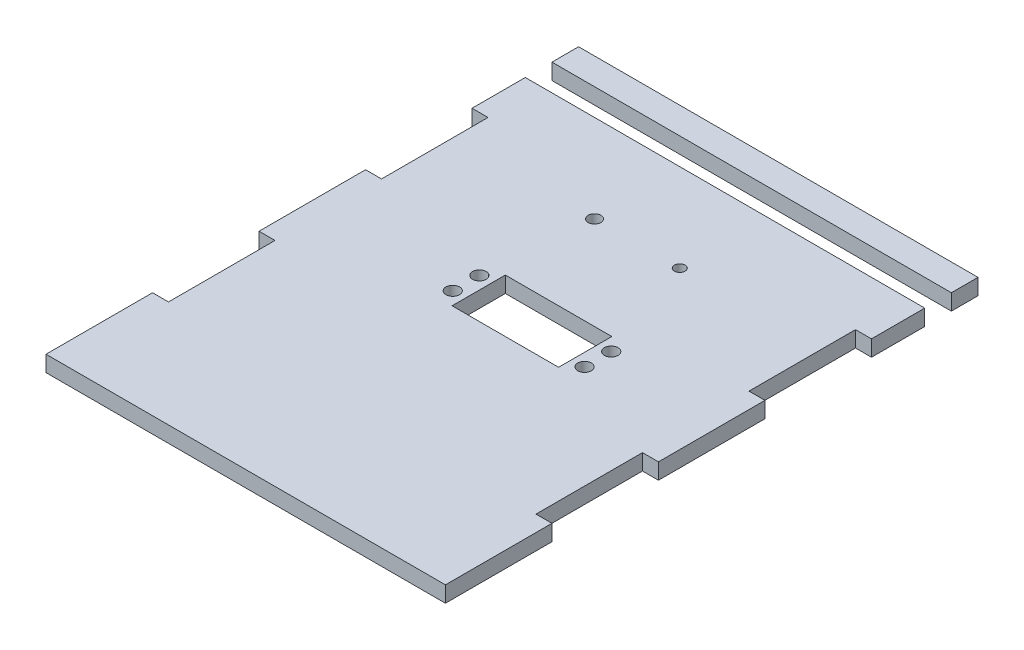
SolidWorks part; units mm, degrees
material "Pine"
ref_plane "Front Plane" through (0, 0, 0) normal (0, 0, 1) x (1, 0, 0)
ref_plane "Top Plane" through (0, 0, 0) normal (0, 1, 0) x (1, 0, 0)
ref_plane "Right Plane" through (0, 0, 0) normal (1, 0, 0) x (0, 0, -1)
sketch "Sketch1" plane through (0, 0, 0) normal (0, 1, 0) x (1, 0, 0)
  line L1 (-75, 100) -> (75, 100)
  line L2 (-75, 100) -> (-75, -100)
  line L3 (-75, -100) -> (75, -100)
  line L4 (75, 100) -> (75, -100)
  line L5 (-75, 100) -> (75, -100) construction
  line L6 (-75, -100) -> (75, 100) construction
  point P0 (0, 0)
  dimension "D1" = 150
  dimension "D2" = 200
extrude "Boss-Extrude1" add sketch "Sketch1" along normal blind 6
sketch "Sketch2" plane through (0, 6, 0) normal (0, 1, 0) x (1, 0, 0)
  line L0 (-75, 100) -> (-75, -100) construction
  line L1 (-75, 60) -> (-69, 60)
  line L2 (-75, 60) -> (-75, 20)
  line L3 (-75, 20) -> (-69, 20)
  line L4 (-69, 60) -> (-69, 20)
  line L5 (75, 100) -> (-75, 100) construction
  line L6 (69, 60) -> (69, 20)
  line L7 (69, 60) -> (75, 60)
  line L8 (75, 60) -> (75, 20)
  line L9 (69, 20) -> (75, 20)
  line L10 (69, -20) -> (69, -60)
  line L11 (69, -20) -> (75, -20)
  line L12 (75, -20) -> (75, -60)
  line L13 (69, -60) -> (75, -60)
  line L14 (-75, -20) -> (-75, -60)
  line L15 (-75, -20) -> (-69, -20)
  line L16 (-69, -20) -> (-69, -60)
  line L17 (-75, -60) -> (-69, -60)
  dimension "D1" = 40
  dimension "D2" = 40
  dimension "D3" = 6
  dimension "D4" = 2
  dimension "D5" = 2
extrude "Cut-Extrude1" cut sketch "Sketch2" against normal blind 6
sketch "Sketch6" plane through (0, 6, 0) normal (0, 1, 0) x (1, 0, 0)
  line L1 (75, -100) -> (75, -60) construction
  circle A0 centre (16, 2) radius 1.23
  dimension "D1" = 2.46
  dimension "D2" = 102
  dimension "D3" = 59
extrude "Cut-Extrude6" cut sketch "Sketch6" against normal through all
sketch "Sketch7" plane through (0, 6, 0) normal (0, 1, 0) x (1, 0, 0)
  line L0 (75, -100) -> (75, -60) construction
  line L1 (-75, -100) -> (75, -100) construction
  circle A0 centre (16, 47) radius 2
  dimension "D1" = 59
  dimension "D2" = 147
extrude "Cut-Extrude7" cut sketch "Sketch7" against normal through all
sketch "Sketch8" plane through (0, 6, 0) normal (0, 1, 0) x (1, 0, 0)
  line L0 (75, 60) -> (75, 100) construction
  line L1 (-75, -100) -> (75, -100) construction
  circle A0 centre (-16, 47) radius 2.38
  dimension "D1" = 91
  dimension "D2" = 147
extrude "Cut-Extrude8" cut sketch "Sketch8" against normal through all
sketch "Sketch9" plane through (0, 6, 0) normal (0, 1, 0) x (1, 0, 0)
  circle A0 centre (30.25, 7) radius 2.55
  circle A1 centre (30.25, -3) radius 2.55
  circle A2 centre (-19.25, 7) radius 2.55
  circle A3 centre (-19.25, -3) radius 2.55
  dimension "D1" = 49.5
  dimension "D2" = 0
  dimension "D3" = 10
  dimension "D4" = 0
  dimension "D5" = 49.5
  dimension "D6" = 0
  dimension "D7" = 93
  dimension "D8" = 55.75
extrude "Cut-Extrude9" cut sketch "Sketch9" against normal through all
sketch "Sketch10" plane through (0, 6, 0) normal (0, 1, 0) x (1, 0, 0)
  line L0 (-75, 100) -> (-75, 60) construction
  line L1 (-75, 90) -> (75, 90)
  line L2 (-75, 90) -> (-75, 80)
  line L3 (-75, 80) -> (75, 80)
  line L4 (75, 90) -> (75, 80)
  line L5 (75, 60) -> (75, 100) construction
  line L6 (75, 100) -> (-75, 100) construction
  dimension "D1" = 10
  dimension "D2" = 10
extrude "Cut-Extrude10" cut sketch "Sketch10" against normal blind 6
extrude "Cut-Extrude11" cut sketch "Sketch11" against normal blind 6
sketch "Sketch11" plane through (0, 6, 0) normal (0, 1, 0) x (1, 0, 0)
  line L1 (-14.5, 12) -> (25.5, 12)
  line L2 (25.5, 12) -> (25.5, -8)
  line L3 (25.5, -8) -> (-14.5, -8)
  line L4 (-14.5, -8) -> (-14.5, 12)
